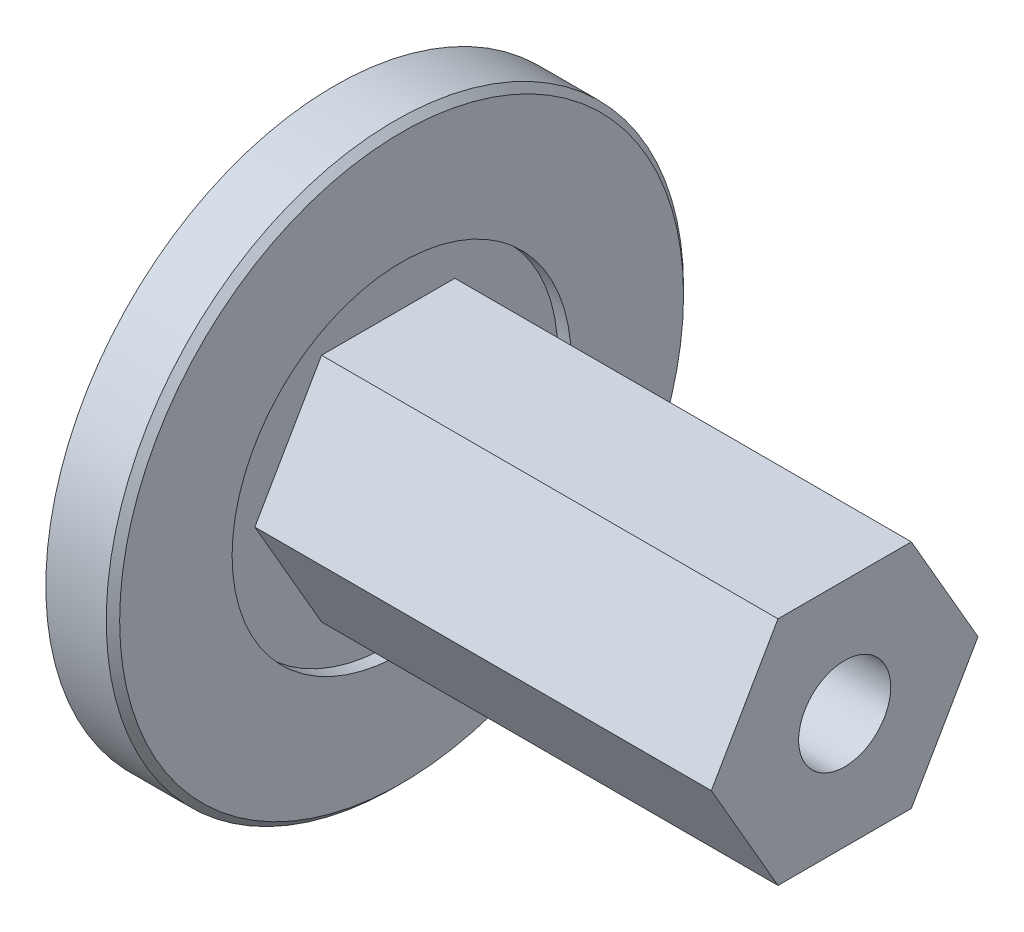
SolidWorks part; units mm, degrees
material "UNOBTANIUM"
ref_plane "Top Plane" through (0, 0, 0) normal (0, 0, 1) x (1, 0, 0)
ref_plane "Right Plane" through (0, 0, 0) normal (0, 1, 0) x (1, 0, 0)
ref_plane "Front Plane" through (0, 0, 0) normal (1, 0, 0) x (0, 0, -1)
ref_axis "x-axis" through (-1.9, 0, 0) along (1, 0, 0)
ref_axis "y-axis" through (0, -23.65, 0) along (0, 1, 0)
ref_axis "z-axis" through (0, 0, 23.65) along (0, 0, -1)
sketch "Sketch1" plane through (0, 0, 0) normal (1, 0, 0) x (0, 0, -1)
  circle A0 centre (0, 0) radius 21.5
  dimension "D1" = 43
extrude "Boss-Extrude1" add sketch "Sketch1" along normal blind 4
sketch "Sketch2" plane through (4, 0, 0) normal (1, 0, 0) x (0, 0, -1)
  circle A0 centre (0, 0) radius 12.625
  circle A1 centre (0, 0) radius 21.5
  circle A2 centre (0, 0) radius 21.5
  dimension "D2" = 25.25
  dimension "D1" = 0
extrude "Boss-Extrude2" add sketch "Sketch2" along normal blind 1
sketch "Sketch3" plane through (0, 0, 0) normal (-1, 0, 0) x (0, 0, 1)
  circle A0 centre (0, 0) radius 3.429
  dimension "D1" = 6.858
extrude "Cut-Extrude1" cut sketch "Sketch3" against normal through all both and the other way through all
sketch "Sketch4" plane through (4, 0, 0) normal (1, 0, 0) x (0, 0, -1)
  line L1 (4.9652, -8.6) -> (9.9304, 0)
  line L2 (9.9304, 0) -> (4.9652, 8.6)
  line L3 (4.9652, 8.6) -> (-4.9652, 8.6)
  line L4 (-4.9652, 8.6) -> (-9.9304, 0)
  line L5 (-9.9304, 0) -> (-4.9652, -8.6)
  line L6 (-4.9652, -8.6) -> (4.9652, -8.6)
  circle A0 centre (0, 0) radius 8.6 construction
  circle A1 centre (0, 0) radius 3.429 construction
  circle A2 centre (0, 0) radius 3.429
  dimension "D1" = 17.2
extrude "Boss-Extrude3" add sketch "Sketch4" along normal blind 34
chamfer "Chamfer1" distance 0.5 angle 45 1 edges at (5, 0, -21.5)
